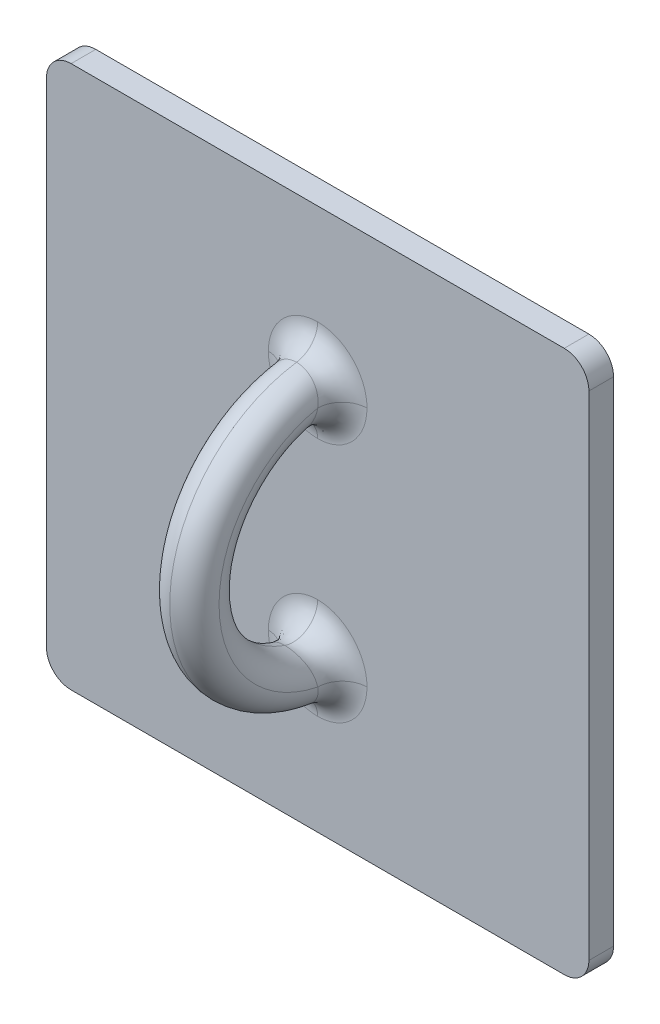
SolidWorks part; units mm, degrees
ref_plane "前视基准面" through (0, 0, 0) normal (0, 0, 1) x (1, 0, 0)
ref_plane "上视基准面" through (0, 0, 0) normal (0, 1, 0) x (1, 0, 0)
ref_plane "右视基准面" through (0, 0, 0) normal (1, 0, 0) x (0, 0, -1)
sketch "草图1" plane through (0, 0, 0) normal (0, 0, 1) x (1, 0, 0)
  line L1 (-11, -11) -> (11, -11)
  line L2 (-11, -11) -> (-11, 11)
  line L3 (-11, 11) -> (11, 11)
  line L4 (11, -11) -> (11, 11)
  line L5 (-11, -11) -> (11, 11) construction
  line L6 (-11, 11) -> (11, -11) construction
  point P0 (0, 0)
  dimension "D1" = 22
  dimension "D2" = 22
extrude "凸台-拉伸1" add sketch "草图1" along normal blind 1
sketch "草图2" plane through (0, 0, 0) normal (1, 0, 0) x (0, 0, -1)
  line L0 (0, 0) -> (-14.4272, 0) construction
  line L1 (-1, 0) -> (-1, 13.9437) construction
  line L2 (-1, -11) -> (-1, 11) construction
  line L3 (-1, 6) -> (-1, -6)
  arc A0 (-1, 6) -> (-1, -6) centre (-1, 0) ccw
  arc A1 (-1, 4) -> (-1, -4) centre (-1, 0) ccw
extrude "凸台-拉伸2" add sketch "草图2" along normal mid plane 2 contours A1 L3 A0 region at (0, 5, 1.1342)
fillet "圆角1" radius 1 4 edges at (11, -11, 0.5) (11, 11, 0.5) (-11, -11, 0.5) (-11, 11, 0.5)
fillet "圆角2" radius 1 4 edges at (1, 0, 7) (-1, 0, 7) (1, 0, 5) (-1, 0, 5)
fillet "圆角3" radius 1 8 edges at (-0.7071, -5.7071, 1) (0.7071, -5.7071, 1) (0.7071, -4.2929, 1) (-0.7071, 4.2929, 1) (0.7071, 4.2929, 1) (0.7071, 5.7071, 1) (-0.7071, -4.2929, 1) (-0.7071, 5.7071, 1)
